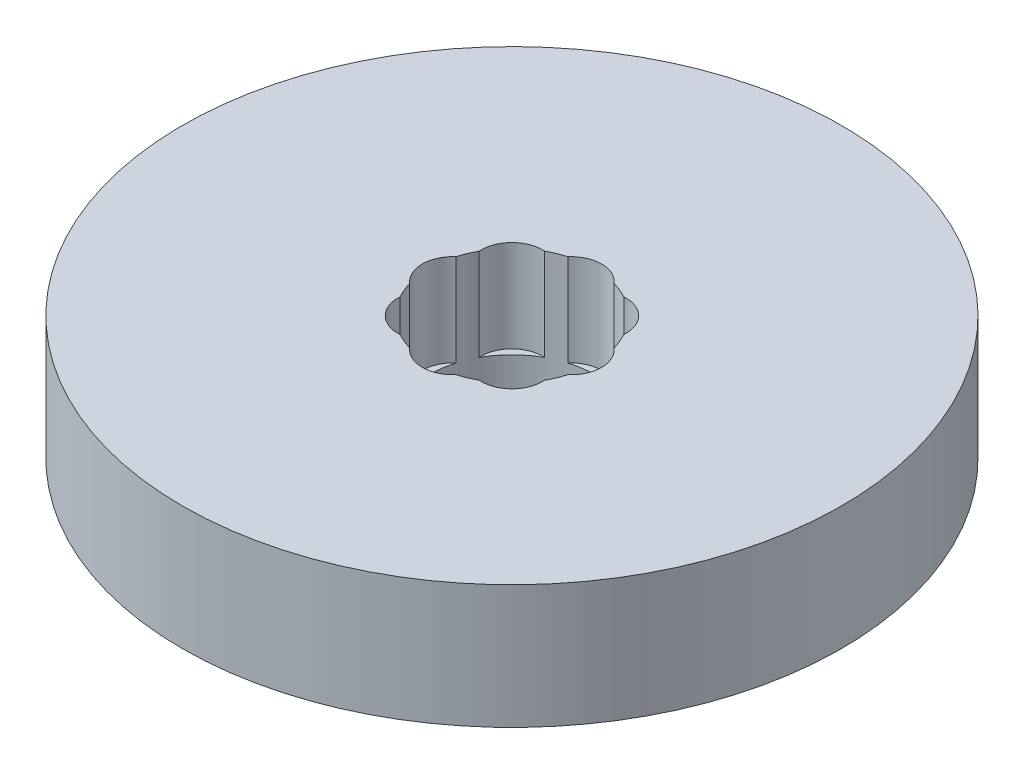
SolidWorks part; units mm, degrees
ref_plane "Front Plane" through (0, 0, 0) normal (0, 0, 1) x (1, 0, 0)
ref_plane "Top Plane" through (0, 0, 0) normal (0, 1, 0) x (1, 0, 0)
ref_plane "Right Plane" through (0, 0, 0) normal (1, 0, 0) x (0, 0, -1)
sketch "Sketch1" plane through (0, 0, 0) normal (0, 1, 0) x (1, 0, 0)
  circle A0 centre (0, 0) radius 80
  dimension "FLANGE_OD" = 160
extrude "Boss-Extrude1" add sketch "Sketch1" along normal blind 30
sketch "Sketch2" plane through (0, 0, 0) normal (0, 1, 0) x (1, 0, 0)
  circle A0 centre (0, 0) radius 20
  dimension "BORE_D" = 40
extrude "Cut-Extrude1" cut sketch "Sketch2" along normal through all
sketch "Sketch3" plane through (0, 30, 0) normal (0, 1, 0) x (1, 0, 0)
  circle A0 centre (0, 0) radius 14.3111 construction
  circle A1 centre (-14.3111, 0) radius 7.4406
  dimension "BOLT_D" = 14.8813
  dimension "BOLT_PCD" = 28.6223
extrude "Cut-Extrude2" cut sketch "Sketch3" against normal blind 22.3451
pattern_circular "CirPattern1" count 8 over 360 about axis through (0, 0, 0) along (0, 1, 0) of "Cut-Extrude2"
